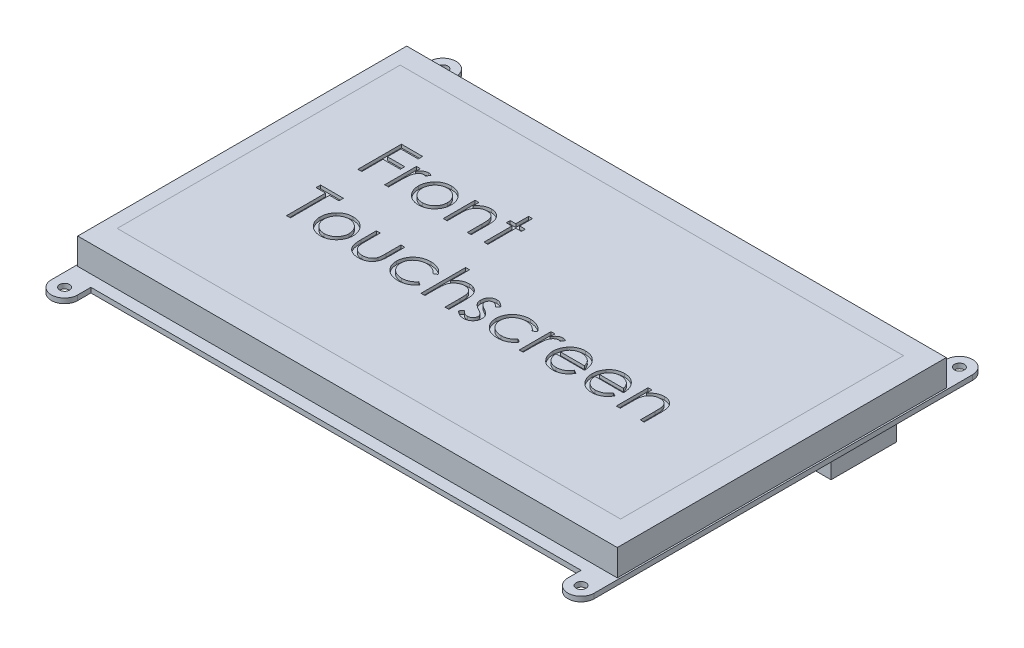
SolidWorks part; units mm, degrees
ref_plane "Front" through (0, 0, 0) normal (0, 0, 1) x (1, 0, 0)
ref_plane "Top" through (0, 0, 0) normal (0, 1, 0) x (1, 0, 0)
ref_plane "Right" through (0, 0, 0) normal (1, 0, 0) x (0, 0, -1)
sketch "Sketch1" plane through (0, 0, 0) normal (0, 1, 0) x (1, 0, 0)
  line L0 (0, 0) -> (12.9315, 0) construction
  line L1 (-74.5, -53.5) -> (74.5, -53.5)
  line L2 (-82.5, -23.8776) -> (-82.5, 23.8776)
  line L3 (-74.5, 53.5) -> (74.5, 53.5)
  line L4 (82.5, -23.8776) -> (82.5, 23.8776)
  line L5 (-82.5, -23.8776) -> (82.5, 23.8776) construction
  line L6 (-82.5, 23.8776) -> (82.5, -23.8776) construction
  line L7 (0, 0) -> (0, 10.1701) construction
  line L8 (82.5, 23.8776) -> (82.5, 57.5)
  line L9 (74.5, 57.5) -> (74.5, 53.5)
  line L10 (-74.5, 57.5) -> (-74.5, 53.5)
  line L11 (-82.5, 23.8776) -> (-82.5, 57.5)
  line L12 (74.5, -57.5) -> (74.5, -53.5)
  line L13 (82.5, -23.8776) -> (82.5, -57.5)
  line L14 (-82.5, -23.8776) -> (-82.5, -57.5)
  line L15 (-74.5, -57.5) -> (-74.5, -53.5)
  circle A0 centre (78.5, 57.5) radius 1.5
  arc A1 (82.5, 57.5) -> (74.5, 57.5) centre (78.5, 57.5) ccw
  arc A2 (-82.5, 57.5) -> (-74.5, 57.5) centre (-78.5, 57.5) cw
  circle A3 centre (-78.5, 57.5) radius 1.5
  arc A4 (82.5, -57.5) -> (74.5, -57.5) centre (78.5, -57.5) cw
  circle A5 centre (78.5, -57.5) radius 1.5
  circle A6 centre (-78.5, -57.5) radius 1.5
  arc A7 (-82.5, -57.5) -> (-74.5, -57.5) centre (-78.5, -57.5) ccw
  point P0 (0, 0)
  point P33 (82.5, 57.5)
  point P34 (74.5, 57.5)
  point P35 (82.5, 57.5)
  dimension "D1" = 3
  dimension "D2" = 112
  dimension "D3" = 154
  dimension "D4" = 2.5
  dimension "D6" = 2.5
  dimension "D5" = 107
  dimension "D7" = 8
extrude "Boss-Extrude1" add sketch "Sketch1" along normal blind 1.5
sketch "Sketch2" plane through (0, 0, 0) normal (0, -1, 0) x (1, 0, 0)
  line L1 (70.6742, -17.8025) -> (79.1702, -17.8025)
  line L2 (70.6742, -17.8025) -> (70.6742, -37.6392)
  line L3 (70.6742, -37.6392) -> (79.1702, -37.6392)
  line L4 (79.1702, -17.8025) -> (79.1702, -37.6392)
  line L5 (70.6742, -17.8025) -> (79.1702, -37.6392) construction
  line L6 (70.6742, -37.6392) -> (79.1702, -17.8025) construction
  line L7 (-18.5141, -5.9976) -> (0, -5.9976)
  line L8 (-18.5141, -5.9976) -> (-18.5141, -15.8759)
  line L9 (-18.5141, -15.8759) -> (0, -15.8759)
  line L10 (0, -5.9976) -> (0, -15.8759)
  line L11 (-18.5141, -5.9976) -> (0, -15.8759) construction
  line L12 (-18.5141, -15.8759) -> (0, -5.9976) construction
  point P0 (74.9222, -27.7209)
  point P5 (-9.2571, -10.9367)
extrude "Boss-Extrude2" add sketch "Sketch2" along normal blind 8
sketch "Sketch3" plane through (0, 1.5, 0) normal (0, 1, 0) x (1, 0, 0)
  line L0 (82.5, -57.5) -> (82.5, 57.5) construction
  line L1 (-82, -50) -> (82, -50)
  line L2 (-82, -50) -> (-82, 50)
  line L3 (-82, 50) -> (82, 50)
  line L4 (82, -50) -> (82, 50)
  line L5 (-82, -50) -> (82, 50) construction
  line L6 (-82, 50) -> (82, -50) construction
  point P0 (0, 0)
  dimension "D1" = 0.5
  dimension "D2" = 100
extrude "Boss-Extrude3" add sketch "Sketch3" along normal blind 8
sketch "Sketch4" plane through (0, 9.5, 0) normal (0, 1, 0) x (1, 0, 0)
  line L0 (82, 50) -> (-82, 50) construction
  line L1 (-78, 44) -> (75, 44)
  line L2 (-78, 44) -> (-78, -42)
  line L3 (-78, -42) -> (75, -42)
  line L4 (75, 44) -> (75, -42)
  line L5 (-82, -50) -> (82, -50) construction
  line L6 (82, -50) -> (82, 50) construction
  line L7 (-82, 50) -> (-82, -50) construction
  dimension "D1" = 6
  dimension "D2" = 8
  dimension "D3" = 7
  dimension "D4" = 4
split line "Split Line1"
sketch "Sketch5" plane through (0, 9.5, 0) normal (0, 1, 0) x (1, 0, 0)
  text T0 "Front\r\nTouchscreen" font "Century Gothic" height in points 50
extrude "Cut-Extrude1" cut sketch "Sketch5" against normal blind 1
